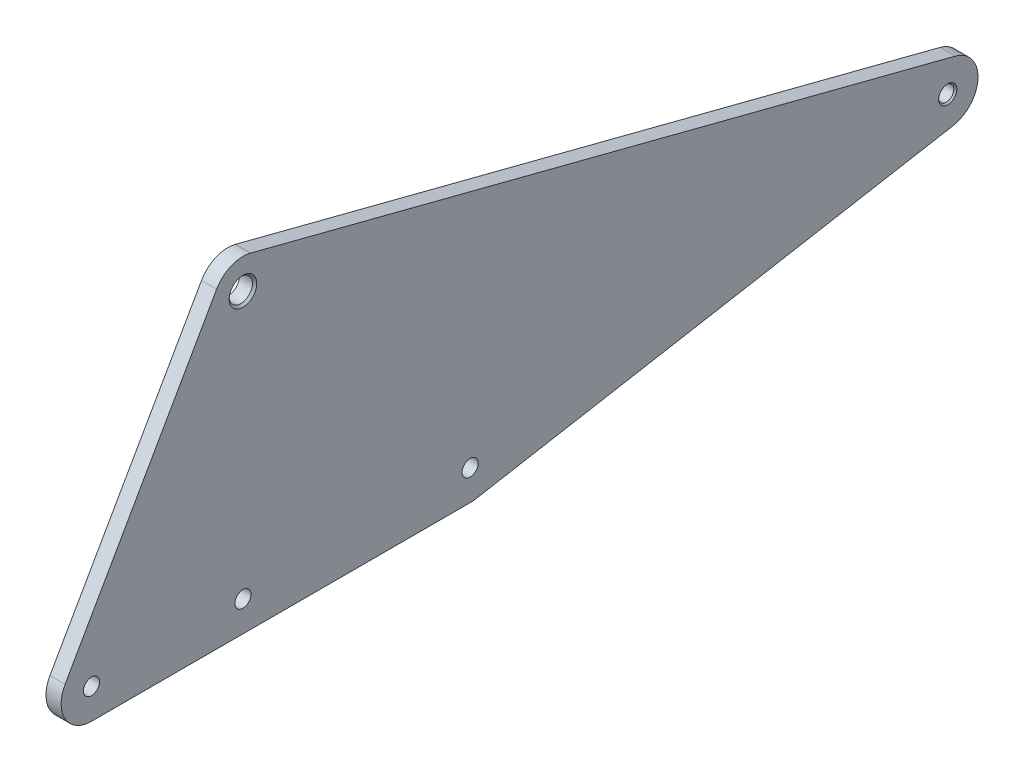
SolidWorks part; units mm, degrees
material "1060 Alloy"
ref_plane "Front Plane" through (0, 0, 0) normal (0, 0, 1) x (1, 0, 0)
ref_plane "Top Plane" through (0, 0, 0) normal (0, 1, 0) x (1, 0, 0)
ref_plane "Right Plane" through (0, 0, 0) normal (1, 0, 0) x (0, 0, -1)
sketch "Sketch1" plane through (0, 0, 0) normal (1, 0, 0) x (0, 0, -1)
  line L0 (-74.539, -105.3537) -> (-11.039, 6.2793)
  line L2 (-63.5, -124.333) -> (95.25, -124.333)
  line L5 (97.4639, -124.1386) -> (297.6159, -88.7056)
  line L6 (298.5742, -63.9025) -> (3.1722, 12.2975)
  arc A0 (3.1722, 12.2975) -> (-11.039, 6.2793) centre (0, 0) ccw
  arc A1 (95.25, -124.333) -> (97.4639, -124.1386) centre (95.25, -111.633) ccw
  arc A2 (-74.539, -105.3537) -> (-63.5, -124.333) centre (-63.5, -111.633) ccw
  arc A3 (297.6159, -88.7056) -> (298.5742, -63.9025) centre (295.402, -76.2) ccw
  point P15 (452.1866, -103.3897)
  point P19 (52.51, -132.0968)
  point P20 (19.5947, 72.9341)
  dimension "D1" = 158.75
  dimension "D2" = 111.633
  dimension "D4" = 25.4
  dimension "D5" = 95.25
  dimension "D7" = 25.4
  dimension "D8" = 295.402
  dimension "D9" = 76.2
extrude "Boss-Extrude1" add sketch "Sketch1" along normal blind 6.35 contours A1 L5 A3 L6 A0 L0 A2 L2
sketch "Sketch2" plane through (6.35, 0, 0) normal (1, 0, 0) x (0, 0, -1)
  circle A0 centre (-63.5, -111.633) radius 3.3782
  circle A1 centre (0, -111.633) radius 3.3782
  circle A2 centre (95.25, -111.633) radius 3.3782
  arc A3 (-74.539, -105.3537) -> (-63.5, -124.333) centre (-63.5, -111.633) ccw construction
  arc A4 (95.25, -124.333) -> (97.4639, -124.1386) centre (95.25, -111.633) ccw construction
  dimension "D2" = 0
  dimension "D3" = 0
  dimension "D4" = 63.5
  dimension "D5" = 6.7564
extrude "Cut-Extrude1" cut sketch "Sketch2" against normal up to next
hole_wizard "3/8 Clearance Hole1" positions "Sketch3" profile "Sketch4" hole size "3/8" standard "ANSI Inch" end condition through all
sketch "Sketch3" plane through (6.35, 0, 0) normal (1, 0, 0) x (0, 0, -1)
  point P0 (0, 0)
sketch "Sketch4" plane through (6.35, 0, 0) normal (0, 1, 0) x (0, 0, -1)
  line L0 (0, 0) -> (0, 6.35)
  line L1 (0, 6.35) -> (4.9022, 6.35)
  line L2 (4.9022, 6.35) -> (4.9022, 0.8915)
  line L3 (4.9022, 0.8915) -> (5.7937, 0)
  line L5 (5.7937, 0) -> (0, 0)
  line L6 (-4.9022, 0.8915) -> (-5.7937, 0) construction
  line L11 (0, -6.35) -> (0, 107.95) construction
  dimension "Thru Hole Dia." = 9.8044
  dimension "Thru Hole Depth" = 6.35
  dimension "Near C'Sink Dia." = 11.5875
  dimension "Near C'Sink Angle" = 90
hole_wizard "1/4 (0.2500) Dowel Hole1" positions "Sketch5" profile "Sketch6" hole size "1/4" standard "ANSI Inch" end condition through all
sketch "Sketch5" plane through (6.35, 0, 0) normal (1, 0, 0) x (0, 0, -1)
  point P0 (295.402, -76.2)
  dimension "D1" = 76.2
  dimension "D2" = 295.402
sketch "Sketch6" plane through (6.35, -76.2, -295.402) normal (0, 1, 0) x (0, 0, -1)
  line L0 (0, 0) -> (0, 6.35)
  line L1 (0, 6.35) -> (3.175, 6.35)
  line L2 (3.175, 6.35) -> (3.175, 0.635)
  line L3 (3.175, 0.635) -> (3.81, 0)
  line L5 (3.81, 0) -> (0, 0)
  line L6 (-3.175, 0.635) -> (-3.81, 0) construction
  line L11 (0, -6.35) -> (0, 107.95) construction
  dimension "Thru Hole Dia." = 6.35
  dimension "Thru Hole Depth" = 6.35
  dimension "Near C'Sink Dia." = 7.62
  dimension "Near C'Sink Angle" = 90
